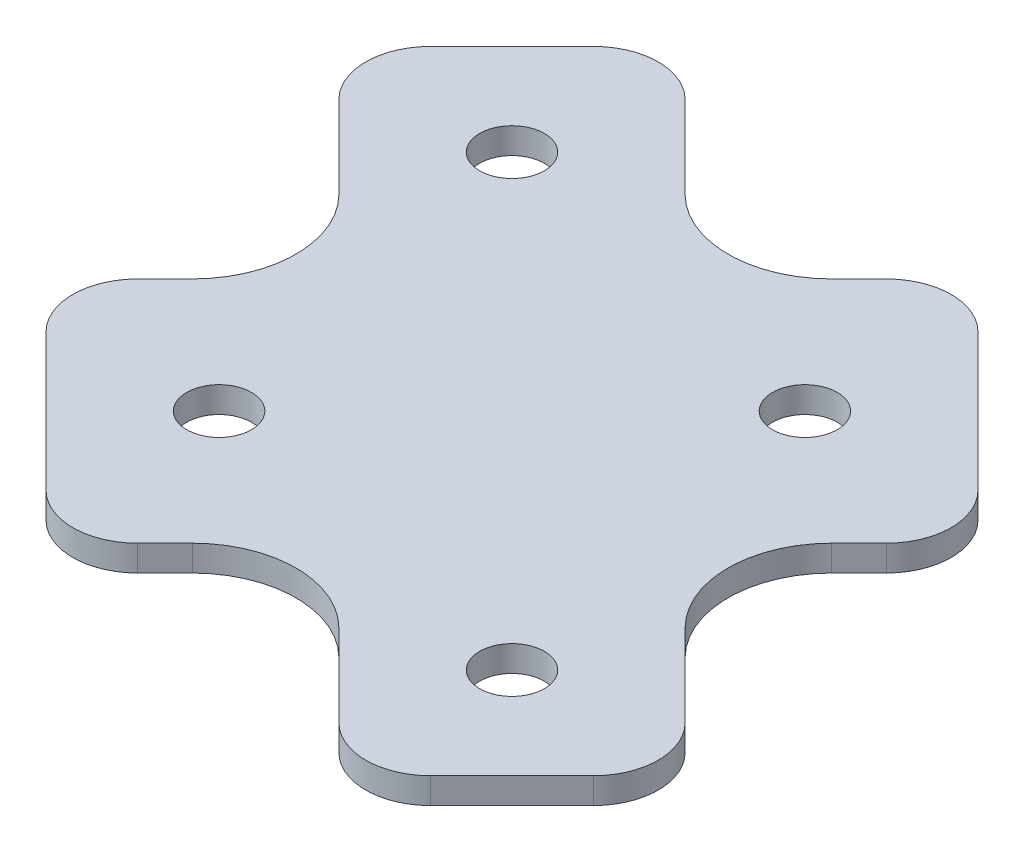
SolidWorks part; units mm, degrees
ref_plane "Front Plane" through (0, 0, 0) normal (0, 0, 1) x (1, 0, 0)
ref_plane "Top Plane" through (0, 0, 0) normal (0, 1, 0) x (1, 0, 0)
ref_plane "Right Plane" through (0, 0, 0) normal (1, 0, 0) x (0, 0, -1)
sketch "Sketch1" plane through (0, 0, 0) normal (0, 1, 0) x (1, 0, 0)
  line L0 (-45.8058, -134.1942) -> (-134.1942, -45.8058)
  line L1 (-90, -90) -> (90, -90) construction
  line L2 (-90, -90) -> (-90, 90) construction
  line L3 (-90, 90) -> (90, 90) construction
  line L4 (90, -90) -> (90, 90) construction
  line L5 (-90, -90) -> (90, 90) construction
  line L6 (-90, 90) -> (90, -90) construction
  line L7 (134.1942, 45.8058) -> (45.8058, 134.1942)
  line L8 (-155.4074, 88.5445) -> (-88.5445, 155.4074)
  line L9 (88.5445, -155.4074) -> (155.4074, -88.5445)
  line L10 (-88.5445, 155.4074) -> (-10.7627, 77.6256)
  line L11 (-10.7627, 77.6256) -> (45.8058, 134.1942)
  line L12 (134.1942, 45.8058) -> (77.6256, -10.7627)
  line L13 (77.6256, -10.7627) -> (155.4074, -88.5445)
  line L14 (88.5445, -155.4074) -> (10.7627, -77.6256)
  line L15 (10.7627, -77.6256) -> (-45.8058, -134.1942)
  line L16 (-155.4074, 88.5445) -> (-77.6256, 10.7627)
  line L17 (-77.6256, 10.7627) -> (-134.1942, -45.8058)
  point P0 (0, 0)
  point P9 (-90, -90)
  point P12 (90, 90)
  point P15 (-121.9759, 121.9759)
  point P18 (121.9759, -121.9759)
  dimension "D1" = 180
  dimension "D2" = 80
  dimension "D3" = 110
  dimension "D4" = 125
extrude "Boss-Extrude1" add sketch "Sketch1" along normal blind 10
sketch "Sketch2" plane through (0, 0, 0) normal (0, -1, 0) x (-1, 0, 0)
  line L0 (134.1942, -45.8058) -> (45.8058, -134.1942) construction
  line L1 (-134.1942, 45.8058) -> (-45.8058, 134.1942) construction
  line L3 (-56.5685, 56.5685) -> (-90, 90) construction
  line L5 (56.5685, -56.5685) -> (90, -90) construction
  circle A1 centre (-56.5685, 56.5685) radius 12.5
  circle A2 centre (56.5685, -56.5685) radius 12.5
  dimension "D1" = 160
  dimension "D2" = 25
extrude "vertical holes" cut sketch "Sketch2" against normal up to surface (10 mm away) up to face at (0, 10, 0)
sketch "Sketch4" plane through (0, 10, 0) normal (0, 1, 0) x (1, 0, 0)
  line L0 (-86.6206, 86.6206) -> (-121.9759, 121.9759) construction
  line L1 (-88.5445, 155.4074) -> (-155.4074, 88.5445) construction
  line L2 (86.6206, -86.6206) -> (121.9759, -121.9759) construction
  line L3 (88.5445, -155.4074) -> (155.4074, -88.5445) construction
  line L4 (-10.7627, 77.6256) -> (-88.5445, 155.4074) construction
  line L5 (90, 90) -> (56.5685, 56.5685) construction
  line L6 (134.1942, 45.8058) -> (45.8058, 134.1942) construction
  circle A0 centre (-86.6206, 86.6206) radius 12.5
  circle A1 centre (86.6206, -86.6206) radius 12.5
  circle A2 centre (56.5685, 56.5685) radius 12.5 construction
  dimension "D1" = 50
extrude "Cut-Extrude1" cut sketch "Sketch4" against normal through all
fillet "Fillet1" radius 40 4 edges at (10.7627, 5, 77.6256) (-77.6256, 5, -10.7627) (77.6256, 5, 10.7627) (-10.7627, 5, -77.6256)
fillet "Fillet2" radius 25 8 edges at (45.8058, 5, -134.1942) (134.1942, 5, -45.8058) (155.4074, 5, 88.5445) (88.5445, 5, 155.4074) (-45.8058, 5, 134.1942) (-134.1942, 5, 45.8058) (-155.4074, 5, -88.5445) (-88.5445, 5, -155.4074)
